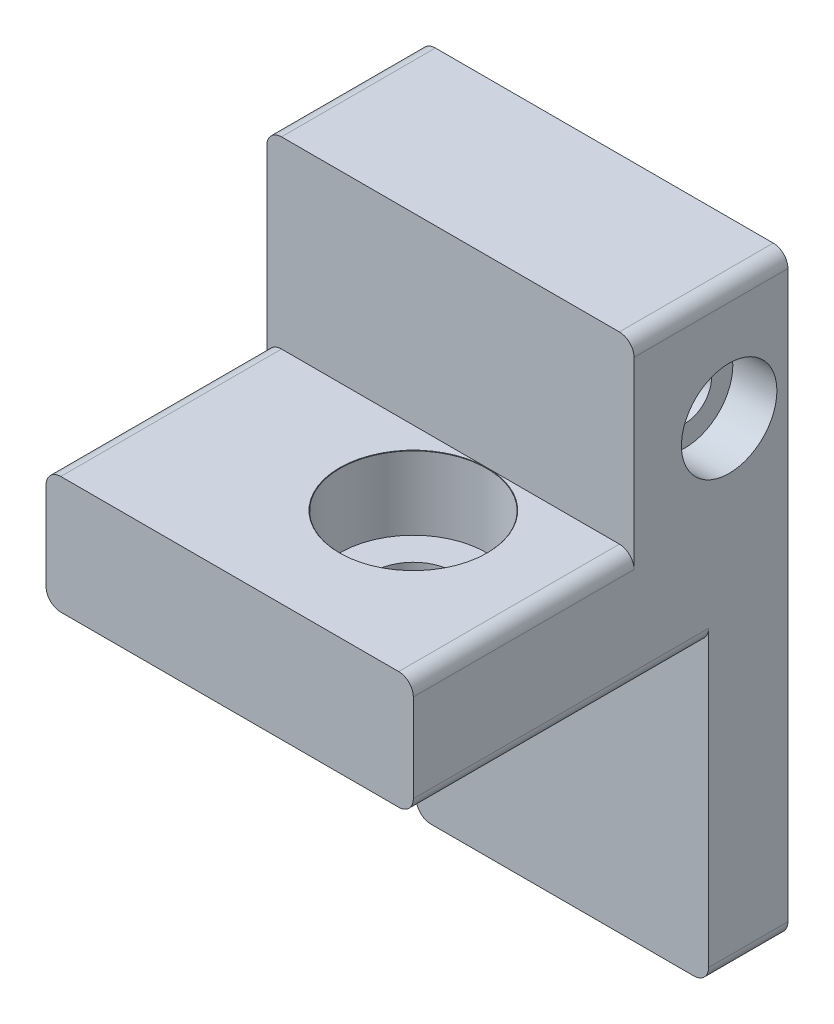
SolidWorks part; units mm, degrees
ref_plane "Front Plane" through (0, 0, 0) normal (0, 0, 1) x (1, 0, 0)
ref_plane "Top Plane" through (0, 0, 0) normal (0, 1, 0) x (1, 0, 0)
ref_plane "Right Plane" through (0, 0, 0) normal (1, 0, 0) x (0, 0, -1)
sketch "Sketch1" plane through (0, 0, 0) normal (0, 1, 0) x (1, 0, 0)
  line L0 (-10, 0) -> (-15, 0)
  line L1 (-10, -20) -> (10, -20)
  line L2 (-10, -20) -> (-10, 0)
  line L3 (-10, 20) -> (10, 20)
  line L4 (10, -20) -> (10, 20)
  line L5 (-10, -20) -> (10, 20) construction
  line L6 (-10, 20) -> (10, -20) construction
  line L7 (-15, 0) -> (-15, 20)
  line L8 (-15, 20) -> (-10, 20)
  point P0 (0, 0)
  dimension "D1" = 20
  dimension "D2" = 40
  dimension "D3" = 20
  dimension "D4" = 5
extrude "Boss-Extrude1" add sketch "Sketch1" along normal blind 8
sketch "Sketch2" plane through (0, 8, 0) normal (0, 1, 0) x (1, 0, 0)
  line L0 (0, -20) -> (0, 20) construction
  line L1 (-10, -20) -> (10, -20) construction
  line L2 (10, 20) -> (-15, 20) construction
  line L3 (-15, 10) -> (10, 10) construction
  line L4 (-15, 20) -> (-15, 0) construction
  line L5 (10, -20) -> (10, 20) construction
  point P14 (0, 10)
  point P15 (0, -10)
  dimension "D2" = 20
hole_wizard "CBORE for M5 SHCS1" positions "Sketch3" profile "Sketch4" counterbore size "M5" standard "ANSI Metric" end condition through all
sketch "Sketch3" plane through (0, 8, 0) normal (0, 1, 0) x (1, 0, 0)
  point P3 (0, 10)
  point P6 (0, -10)
sketch "Sketch4" plane through (0, 8, -10) normal (1, 0, 0) x (0, 0, 1)
  line L0 (0, 0) -> (0, 8)
  line L1 (0, 8) -> (2.75, 8)
  line L3 (2.75, 8) -> (2.75, 5)
  line L4 (5, 5) -> (2.75, 5)
  line L5 (5, 5) -> (5, 0.025)
  line L6 (5, 0.025) -> (5.025, 0)
  line L7 (5.025, 0) -> (0, 0)
  line L8 (-5, 0.025) -> (-5.025, 0) construction
  line L11 (0, -6.35) -> (0, 107.95) construction
  dimension "Thru Hole Dia." = 5.5
  dimension "Thru Hole Depth" = 8
  dimension "C'Bore Dia." = 10
  dimension "C'Bore Depth" = 5
  dimension "Near C'Sink Dia." = 10.05
  dimension "Near C'Sink Angle" = 90
sketch "Sketch5" plane through (0, 8, 0) normal (0, 1, 0) x (1, 0, 0)
  line L0 (10, -20) -> (10, 20) construction
  line L1 (-15, 18) -> (10, 18)
  line L2 (-15, 18) -> (-15, 15.025)
  line L3 (-15, 15.025) -> (10, 15.025)
  line L4 (10, 18) -> (10, 15.025)
  line L5 (10, 20) -> (-15, 20) construction
  line L6 (-15, 20) -> (-15, 0) construction
  circle A0 centre (0, 10) radius 5.025 construction
  dimension "D1" = 2
extrude "Boss-Extrude2" add sketch "Sketch5" along normal blind 12.51
sketch "Sketch6" plane through (0, 0, -18) normal (0, 0, -1) x (-1, 0, 0)
  line L0 (15, 20.51) -> (15, 8) construction
  line L1 (-10, 20.51) -> (15, 20.51)
  line L2 (-10, 20.51) -> (-10, 20)
  line L3 (-5, 17.51) -> (15, 17.51)
  line L4 (15, 20.51) -> (15, 17.51)
  line L5 (-5, 17.51) -> (-5, 8)
  line L6 (15, 8) -> (-10, 8) construction
  line L7 (-5, 8) -> (-10, 8)
  line L8 (-10, 8) -> (-10, 20)
  line L9 (15, 16.01) -> (12, 16.01)
  line L10 (12, 16.01) -> (12, 8)
  line L11 (-10, 8) -> (15, 8) construction
  line L12 (12, 8) -> (15, 8)
  line L13 (15, 8) -> (15, 16.01)
  dimension "D1" = 3
  dimension "D2" = 3
  dimension "D3" = 1.5
  dimension "D4" = 5
extrude "Boss-Extrude3" add sketch "Sketch6" along normal blind 7.5
sketch "Sketch7" plane through (0, 0, -20) normal (0, 0, -1) x (-1, 0, 0)
  line L6 (-10, 0) -> (15, 0)
  line L7 (15, 0) -> (15, 8)
  line L8 (15, 8) -> (12, 8)
  line L9 (12, 8) -> (-5, 8)
  line L10 (-5, 8) -> (-10, 8)
  line L11 (-10, 8) -> (-10, 0)
  line L12 (-10, 0) -> (15, 0)
  line L13 (15, 0) -> (15, 8)
  line L14 (15, 8) -> (12, 8)
  line L15 (12, 8) -> (-5, 8)
  line L16 (-5, 8) -> (-10, 8)
  line L17 (-10, 8) -> (-10, 0)
  dimension "D1" = 0
extrude "Boss-Extrude4" add sketch "Sketch7" along normal up to surface (5.5 mm away) up to face at (0, 15.34, -25.5)
sketch "Sketch8" plane through (0, 0, -18) normal (0, 0, -1) x (-1, 0, 0)
  line L0 (12, 16.01) -> (12, 8) construction
  line L1 (-5, 8) -> (12, 8)
  line L2 (-5, 8) -> (-5, 9.25)
  line L3 (-5, 9.25) -> (12, 9.25)
  line L4 (12, 8) -> (12, 9.25)
  dimension "D1" = 1.25
extrude "Boss-Extrude5" add sketch "Sketch8" along normal up to surface (7.5 mm away) up to face at (-5.4, 12.406, -25.5)
sketch "Sketch9" plane through (0, 0, -25.5) normal (0, 0, -1) x (-1, 0, 0)
  line L0 (-10, 0) -> (15, 0)
  line L1 (15, 0) -> (15, -5.4)
  line L2 (15, -5.4) -> (9.9, -5.4)
  line L3 (9.9, -5.4) -> (9.9, -20)
  line L4 (9.9, -20) -> (-10, -20)
  line L5 (-10, -20) -> (-10, 0)
  dimension "D1" = 5.4
  dimension "D2" = 5.1
  dimension "D3" = 20
extrude "Boss-Extrude6" add sketch "Sketch9" against normal blind 5.4
fillet "Fillet2" radius 1 10 edges at (-15, 0, -10.05) (10, 0, -0.05) (-10, 8, 10) (-15, 8, -7.5125) (10, 8, 2.4875) (-15, 20.51, -20.2625) (10, 20.51, -20.2625) (-15, -5.4, -22.8) (-9.9, -20, -22.8) (10, -20, -22.8)
sketch "Sketch10" plane through (10, 0, 0) normal (1, 0, 0) x (0, 0, -1)
  circle A0 centre (21.5, 12.68) radius 2.35 construction
  circle A1 centre (21.5, 12.68) radius 2.35
hole_wizard "CBORE for M3 SHCS1" positions "Sketch11" profile "Sketch12" counterbore size "M3" standard "ANSI Metric" end condition up to next
sketch "Sketch11" plane through (10, 0, 0) normal (1, 0, 0) x (0, 0, -1)
  point P0 (21.5, 12.68)
sketch "Sketch12" plane through (10, 12.68, -21.5) normal (0, 1, 0) x (0, 0, -1)
  line L0 (0, 0) -> (0, 5)
  line L1 (0, 5) -> (1.8, 5)
  line L3 (1.8, 5) -> (1.8, 3)
  line L4 (1.8, 3) -> (3.25, 3)
  line L5 (3.25, 3) -> (3.25, 0)
  line L7 (3.25, 0) -> (0, 0)
  line L11 (0, -6.35) -> (0, 107.95) construction
  dimension "Thru Hole Dia." = 3.6
  dimension "Thru Hole Depth" = 5
  dimension "C'Bore Dia." = 6.5
  dimension "C'Bore Depth" = 3
sketch "Sketch13" plane through (0, 0, -25.5) normal (0, 0, -1) x (-1, 0, 0)
  line L0 (-10, 7) -> (-10, 1) construction
  line L1 (-10, 7) -> (-10, 1) construction
  line L2 (-10, 4) -> (15, 4) construction
  line L3 (15, -4.4) -> (15, 16.01) construction
  line L4 (2.5, 20.51) -> (2.5, -20) construction
  line L5 (14, 20.51) -> (-9, 20.51) construction
  line L6 (-9, -20) -> (8.9, -20) construction
  circle A0 centre (10, 4) radius 2.4
  circle A1 centre (-5, 4) radius 2.4
  point P6 (10, 4)
  point P7 (-5, 4)
  point P14 (2.5, 4)
  dimension "D3" = 4.8
  dimension "D1" = 15
  dimension "D2" = 7.5
extrude "Cut-Extrude1" cut sketch "Sketch13" against normal blind 3.8
sketch "Sketch14" plane through (0, 0, -21.7) normal (0, 0, -1) x (-1, 0, 0)
  circle A0 centre (-5, 4) radius 1.65
  circle A1 centre (10, 4) radius 1.65
  dimension "D1" = 3.3
extrude "Cut-Extrude2" cut sketch "Sketch14" against normal blind 3
sketch "Sketch15" plane through (0, 8, 0) normal (0, 1, 0) x (1, 0, 0)
  line L1 (-10, 0) -> (10, 0)
  line L2 (-10, 0) -> (-10, -20)
  line L3 (-10, -20) -> (10, -20)
  line L4 (10, 0) -> (10, -20)
extrude "Cut-Extrude3" cut sketch "Sketch15" against normal through all
